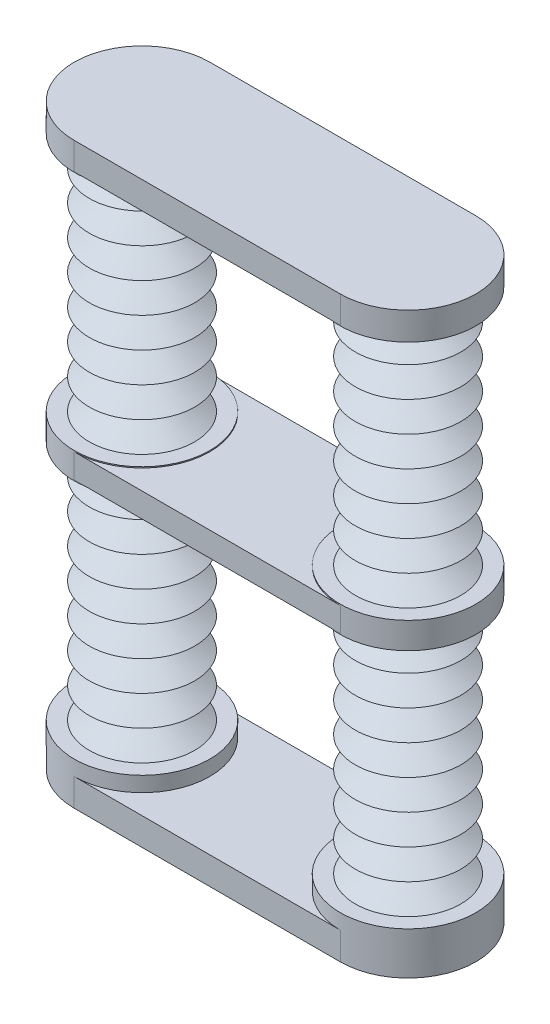
SolidWorks part; units mm, degrees
ref_plane "Front Plane" through (0, 0, 0) normal (0, 0, 1) x (1, 0, 0)
ref_plane "Top Plane" through (0, 0, 0) normal (0, 1, 0) x (1, 0, 0)
ref_plane "Right Plane" through (0, 0, 0) normal (1, 0, 0) x (0, 0, -1)
sketch "Sketch1" plane through (0, 0, 0) normal (0, 0, 1) x (1, 0, 0)
  line L0 (-166.5994, 5.0111) -> (58.4006, 5.0111)
  line L1 (58.4006, 5.0111) -> (58.4006, 55.0111)
  line L2 (58.4006, 55.0111) -> (-41.5994, 55.0111)
  line L3 (-41.5994, 55.0111) -> (45.0031, 105.0111)
  line L4 (45.0031, 105.0111) -> (-41.5994, 155.0111)
  line L5 (-41.5994, 155.0111) -> (45.0031, 205.0111)
  line L6 (-41.5994, 255.0111) -> (45.0031, 305.0111)
  line L7 (45.0031, 305.0111) -> (-41.5994, 355.0111)
  line L8 (-41.5994, 355.0111) -> (45.0031, 405.0111)
  line L9 (45.0031, 205.0111) -> (-41.5994, 255.0111)
  line L10 (-116.5994, 55.0111) -> (-29.9969, 105.0111)
  line L11 (-29.9969, 105.0111) -> (-116.5994, 155.0111)
  line L12 (-116.5994, 155.0111) -> (-29.9969, 205.0111)
  line L13 (-116.5994, 255.0111) -> (-29.9969, 305.0111)
  line L14 (-29.9969, 305.0111) -> (-116.5994, 355.0111)
  line L15 (-116.5994, 355.0111) -> (-29.9969, 405.0111)
  line L16 (-29.9969, 205.0111) -> (-116.5994, 255.0111)
  line L17 (-166.5994, 5.0111) -> (-166.5994, 55.0111)
  line L18 (-166.5994, 55.0111) -> (-116.5994, 55.0111)
  line L22 (45.0031, 405.0111) -> (-41.5876, 454.8817)
  line L26 (-29.9969, 405.0111) -> (-116.5876, 454.8817)
  line L41 (-116.5876, 454.8817) -> (-41.5876, 454.8817)
revolve "Revolve1" add sketch "Sketch1" angle 360 about L1
mirror "Mirror1" about plane through (-116.5876, 454.8817, 0) normal (0, -1, 0) of "Revolve1"
ref_plane "Plane2" through (500, 0, 0) normal (1, 0, 0) x (0, 0, -1)
mirror "Mirror25" about plane through (500, 0, 0) normal (1, 0, 0) of bodies 102
ref_plane "Plane3" through (0, 11.3667, 0) normal (0, 1, 0) x (1, 0, 0)
sketch "Sketch11" plane through (0, 11.3667, 0) normal (0, 1, 0) x (1, 0, 0)
  line L1 (58.4006, 225) -> (941.5994, 225)
  line L2 (58.4006, 225) -> (58.4006, -225)
  line L3 (58.4006, -225) -> (941.5994, -225)
  line L4 (941.5994, 225) -> (941.5994, -225)
  circle A2 centre (58.4006, 0) radius 225
  circle A3 centre (941.5994, 0) radius 225
mirror "Mirror28" about plane through (0, 11.3667, 0) normal (0, 1, 0) of bodies 102 103
combine bodies "Combine2" operation type add bodies to combine 102 104
combine bodies "Combine3" operation type add bodies to combine 103 105
ref_plane "Plane5" through (0, 904.7523, 0) normal (0, 1, 0) x (1, 0, 0)
ref_plane "Plane6" through (0, -882.0188, 0) normal (0, -1, 0) x (-1, 0, 0)
sketch "Sketch22" plane through (0, 904.7523, 0) normal (0, 1, 0) x (1, 0, 0)
  line L0 (58.4006, 225) -> (941.5994, 225)
  line L1 (941.5994, 225) -> (941.5994, -225)
  line L2 (941.5994, -225) -> (58.4006, -225)
  line L3 (58.4006, -225) -> (58.4006, 225)
  circle A0 centre (58.4006, 0) radius 225 construction
  circle A1 centre (941.5994, 0) radius 225 construction
  circle A2 centre (58.4006, 0) radius 225
  circle A3 centre (941.5994, 0) radius 225
  point P13 (-475.7053, -905.2778)
  point P14 (0, 0)
  circle M1 centre (58.4006, 0) radius 225
sketch "Sketch23" plane through (0, -882.0188, 0) normal (0, -1, 0) x (-1, 0, 0)
  line L0 (-941.5994, 225) -> (-58.4006, 225)
  line L1 (-58.4006, 225) -> (-58.4006, -225)
  line L2 (-58.4006, -225) -> (-941.5994, -225)
  line L3 (-941.5994, -225) -> (-941.5994, 225)
  circle A0 centre (-941.5994, 0) radius 225 construction
  circle A1 centre (-58.4006, 0) radius 225 construction
  circle A2 centre (-941.5994, 0) radius 225
  circle A3 centre (-58.4006, 0) radius 225
extrude "Boss-Extrude9" add sketch "Sketch23" along normal blind 91.3189 contours L3 A2 | L3 A2 | A3 L0 A2 L2 | L1 A3 | L1 A3 region at (846.1064, -882.0188, 0) region at (500, -882.0188, 0) region at (1037.0924, -882.0188, 0) region at (-37.0924, -882.0188, 0) region at (153.8936, -882.0188, 0)
extrude "Boss-Extrude10" add sketch "Sketch11" along normal blind 40 and the other way blind 40.5443 contours L1 L4 L3 L2
extrude "Boss-Extrude11" add sketch "Sketch22" along normal blind 42 and the other way blind 48 contours L3 M1 | L1 A3 | L2 L3 L0 L1 region at (-37.0924, 904.7523, 0) region at (1037.0924, 904.7523, 0)
scale "Scale1" scale about centroid uniform scaling yes scale factor 0.055
ref_plane "Plane4" through (0, -1782.0188, 0) normal (0, -1, 0) x (-1, 0, 0)
sketch "Sketch16" plane through (0, -1782.0188, 0) normal (0, -1, 0) x (-1, 0, 0)
  line L1 (-941.1415, 225) -> (-57.9426, 225)
  line L2 (-941.1415, 225) -> (-941.1415, -225)
  line L3 (-941.1415, -225) -> (-57.9426, -225)
  line L4 (-57.9426, 225) -> (-57.9426, -225)
  circle A2 centre (-941.1415, 0) radius 225
  circle A3 centre (-57.9426, 0) radius 225
sketch "Sketch17" plane through (0, -1782.0188, 0) normal (0, -1, 0) x (-1, 0, 0)
  line L1 (-1187.3914, -604.724) -> (240.8279, -604.724)
  line L2 (-1187.3914, -604.724) -> (-1187.3914, 956.7712)
  line L3 (-1187.3914, 956.7712) -> (240.8279, 956.7712)
  line L4 (240.8279, -604.724) -> (240.8279, 956.7712)
